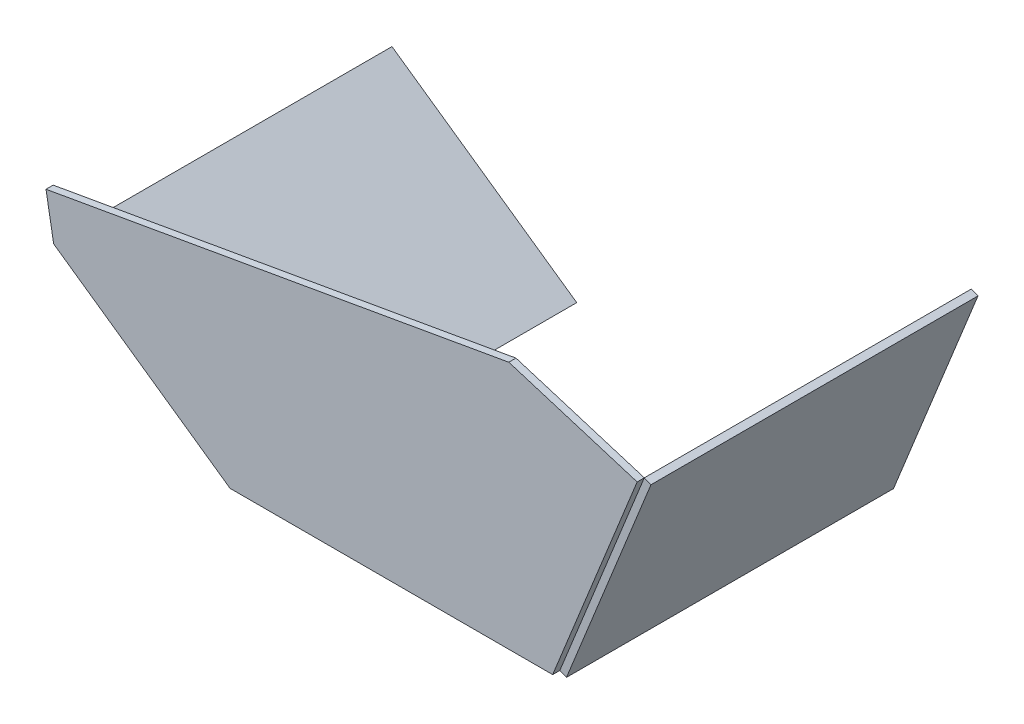
SolidWorks part; units mm, degrees
material "Melamine"
ref_plane "Front Plane" through (0, 0, 0) normal (0, 0, 1) x (1, 0, 0)
ref_plane "Top Plane" through (0, 0, 0) normal (0, 1, 0) x (1, 0, 0)
ref_plane "Right Plane" through (0, 0, 0) normal (1, 0, 0) x (0, 0, -1)
ref_axis "Axis1" through (0, 0, -14.8175) along (0, 0, 1)
sketch "Sketch1" plane through (0, 0, 0) normal (0, 0, 1) x (1, 0, 0)
  line L0 (-137.5, 0) -> (137.5, 0) construction
  line L1 (-137.5, 0) -> (-301.3304, 114.7153)
  line L4 (-148.5709, 0) -> (-304.9726, 109.5137)
  line L5 (-304.9726, 109.5137) -> (-301.3304, 114.7153)
  line L12 (137.5, 0) -> (212.4213, 185.4368) construction
  line L13 (137.5, 0) -> (143.3876, -2.3788)
  line L14 (143.3876, -2.3788) -> (218.3089, 183.058)
  line L15 (218.3089, 183.058) -> (212.4213, 185.4368)
  line L16 (212.4213, 185.4368) -> (137.5, 0)
  line L17 (-137.5, 0) -> (-148.5709, 0)
  point P3 (0, 0)
  point P4 (0, 0)
  point P8 (0, 0)
  point P10 (-137.5, 0.7073)
  dimension "D1" = 35
  dimension "D2" = 275
  dimension "D4" = 200
  dimension "D6" = 6.35
  dimension "D7" = 68
  dimension "D8" = 200
  dimension "D9" = 6.35
extrude "Boss-Extrude1" add sketch "Sketch1" along normal blind 290
sketch "Sketch2" plane through (0, 0, 290) normal (0, 0, 1) x (1, 0, 0)
  line L1 (-311.7783, 148.1104) -> (98.6242, 220.4754)
  line L3 (137.5, 0) -> (-148.5709, 0)
  line L5 (137.5, 0) -> (212.4213, 185.4368)
  line L7 (-304.9726, 109.5137) -> (-311.7783, 148.1104)
  line L8 (-301.3304, 114.7153) -> (-304.9726, 109.5137) construction
  line L9 (212.4213, 185.4368) -> (98.6242, 220.4754)
  line L10 (137.5, 0) -> (98.6242, 220.4754) construction
  line L11 (-304.9726, 109.5137) -> (-148.5709, 0)
  line L13 (-304.9726, 109.5137) -> (-148.5709, 0) construction
  point P0 (-144.352, 1.1422)
  point P4 (-309.5675, 102.9516)
  dimension "D1" = 10
  dimension "D2" = 200
extrude "Boss-Extrude2" add sketch "Sketch2" along normal blind 6.35 separate body
ref_plane "Plane1" through (0, 0, 0) normal (0.9848, 0.1736, 0) x (0, 0, 1)
